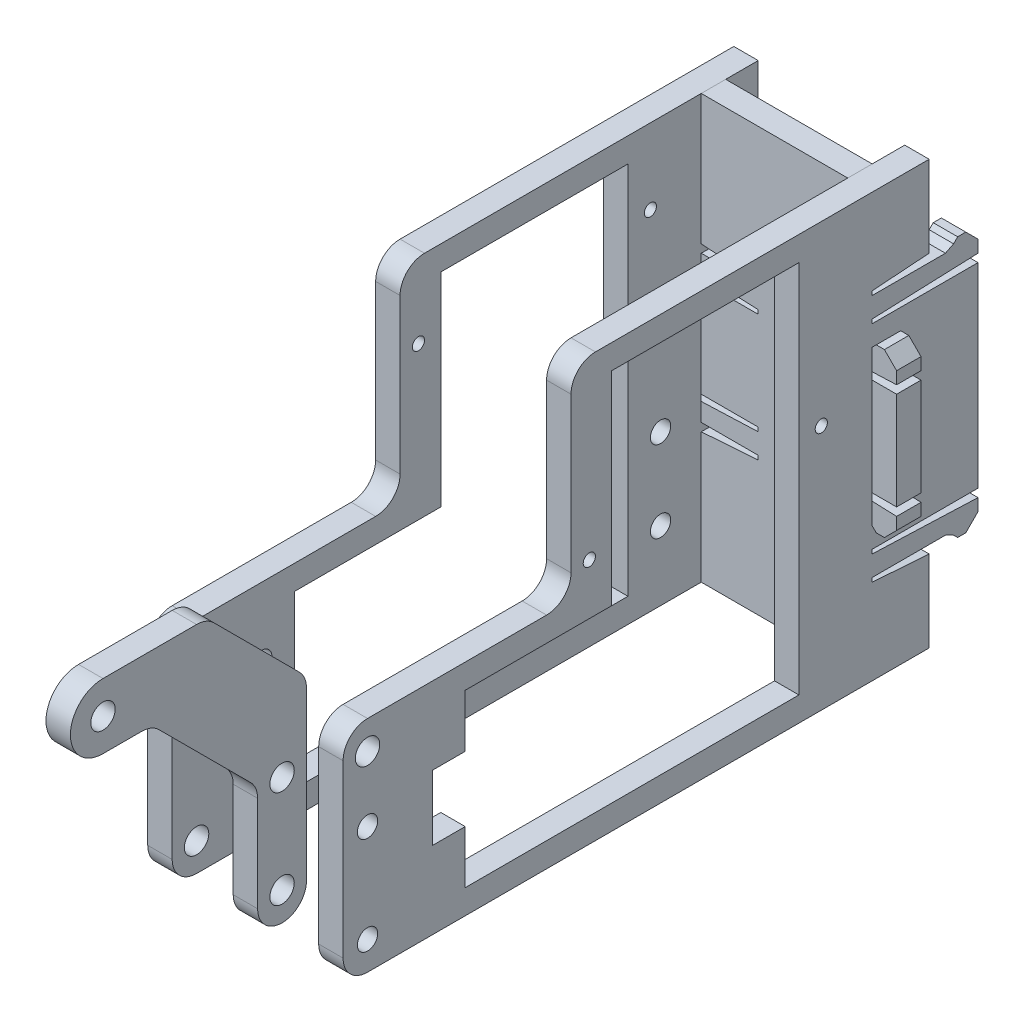
SolidWorks part; units mm, degrees
material "Lasercut ABS"
ref_plane "Front Plane" through (0, 0, 0) normal (0, 0, 1) x (1, 0, 0)
ref_plane "Top Plane" through (0, 0, 0) normal (0, 1, 0) x (1, 0, 0)
ref_plane "Right Plane" through (0, 0, 0) normal (1, 0, 0) x (0, 0, -1)
ref_plane "Plane1" through (9, 0, 0) normal (1, 0, 0) x (0, 0, -1)
ref_plane "Plane2" through (-9, 0, 0) normal (1, 0, 0) x (0, 0, -1)
sketch "Sketch1" plane through (9, 0, 0) normal (1, 0, 0) x (0, 0, -1)
  line L0 (6, 38) -> (6, 14)
  line L1 (0, 10) -> (0, 0)
  line L2 (0, 0) -> (-72, 0)
  line L3 (0, 42) -> (0, 52)
  line L4 (0, 52) -> (-44, 52)
  line L5 (-57, 17.5) -> (-57, 24)
  line L6 (-7, 35) -> (-4, 35)
  line L7 (-7, 35) -> (-7, 17)
  line L8 (-7, 17) -> (-4, 17)
  line L9 (-4, 35) -> (-4, 17)
  line L10 (-57, 3) -> (-16, 3)
  line L11 (-57, 3) -> (-57, 9.5)
  line L12 (-57, 24) -> (-16, 24) construction
  line L13 (-16, 3) -> (-16, 24) construction
  line L14 (-57, 3) -> (-16, 24) construction
  line L15 (-57, 24) -> (-16, 3) construction
  line L16 (-61, 17.5) -> (-57, 17.5)
  line L17 (-61, 17.5) -> (-61, 9.5)
  line L18 (-57, 24) -> (-39, 24)
  line L19 (-39, 24) -> (-39, 49)
  line L20 (-39, 49) -> (-16, 49)
  line L21 (-16, 49) -> (-16, 3)
  line L22 (-72, 0) -> (-72, 27)
  line L23 (-72, 27) -> (-44, 27)
  line L24 (-44, 27) -> (-44, 52)
  line L25 (-27.5, 49) -> (-27.5, 30.25) construction
  line L26 (-41.75, 30.25) -> (-13.25, 30.25) construction
  line L27 (-69, 23.5) -> (-69, 3.5) construction
  line L28 (-69, 13.5) -> (-72, 13.5) construction
  line L29 (-61, 9.5) -> (-57, 9.5)
  circle A0 centre (-69, 15.5) radius 1.25
  circle A4 centre (-41.75, 30.25) radius 0.75
  circle A5 centre (-13.25, 30.25) radius 0.75
  circle A6 centre (-69, 23.5) radius 1.5
  circle A7 centre (-69, 3.5) radius 1.25
  point P12 (-36.5, 13.5)
  point P38 (-27.5, 30.25)
  line B0 (-7, 10.5) -> (0, 10)
  line B1 (-7, 11) -> (-7, 10.5)
  line B2 (2, 11) -> (-7, 11)
  line B3 (3, 10.5) -> (2, 11)
  line B4 (3.5, 10) -> (3, 10.5)
  line B5 (4.5, 10) -> (3.5, 10)
  line B6 (6, 11.5) -> (4.5, 10)
  line B7 (6, 13) -> (6, 11.5)
  line B8 (-7, 14) -> (-7, 13.5)
  line B9 (-7, 13.5) -> (6, 13)
  line B10 (6, 14) -> (-7, 14)
  line B11 (6, 38) -> (-7, 38)
  line B12 (-7, 38) -> (-7, 38.5)
  line B13 (-7, 38.5) -> (6, 39)
  line B14 (6, 39) -> (6, 40.5)
  line B15 (6, 40.5) -> (4.5, 42)
  line B16 (4.5, 42) -> (3.5, 42)
  line B17 (3.5, 42) -> (3, 41.5)
  line B18 (3, 41.5) -> (2, 41)
  line B19 (2, 41) -> (-7, 41)
  line B20 (-7, 41) -> (-7, 41.5)
  line B21 (-7, 41.5) -> (0, 42)
  dimension "D7" = 8
  dimension "D15" = 1.5
  dimension "D20" = 3
  dimension "D9" = 2.5
  dimension "D1" = 10
  dimension "D2" = 3
  dimension "D3" = 3
  dimension "D4" = 3
  dimension "D5" = 41
  dimension "D6" = 21
  dimension "D8" = 4
  dimension "D10" = 3
  dimension "D11" = 9
  dimension "D12" = 23
  dimension "D13" = 25
  dimension "D14" = 3
  dimension "D16" = 28.5
  dimension "D17" = 18.75
  dimension "D18" = 5
  dimension "D19" = 3
  dimension "D21" = 20
  dimension "D22" = 12
  dimension "D23" = 3
  dimension "D24" = 8
sketch_block_instance "Block-Snap-L-1"
sketch_block "Block-Snap-L" parameters "D1"=13, "D2"=0.5, "D3"=1, "D4"=1.5, "D5"=1.5, "D6"=0.5, "D7"=1, "D8"=7, "D9"=1, "D10"=0.5, "D11"=1, "D12"=1.5, "D13"=2.5
sketch_block_instance "Block-Snap-R-1"
sketch_block "Block-Snap-R" parameters "D1"=13, "D2"=0.5, "D3"=1, "D4"=0.5, "D5"=1, "D6"=2.5, "D7"=1.5, "D8"=1.5, "D9"=1.5, "D10"=1, "D11"=0.5, "D12"=1, "D13"=7
extrude "Boss-Extrude1" add sketch "Sketch1" along normal blind 3
sketch "Sketch2" plane through (-9, 0, 0) normal (1, 0, 0) x (0, 0, -1)
  line L0 (-4, 35) -> (-4, 17) construction
  line L1 (-7, 35) -> (-4, 35) construction
  line L2 (-7, 35) -> (-7, 17) construction
  line L3 (-7, 17) -> (-4, 17) construction
  line L4 (-16, 49) -> (-16, 3) construction
  line L5 (-39, 49) -> (-16, 49) construction
  line L6 (-39, 24) -> (-39, 49) construction
  line L7 (-16, 3) -> (-57, 24) construction
  line L9 (-57, 3) -> (-16, 3) construction
  line L10 (0, 0) -> (-72, 0) construction
  line L11 (-72, 0) -> (-72, 27) construction
  line L12 (-72, 27) -> (-44, 27) construction
  line L13 (-44, 27) -> (-44, 52) construction
  line L14 (0, 52) -> (-44, 52) construction
  line L15 (0, 42) -> (0, 52) construction
  line L16 (-7, 41.5) -> (0, 42) construction
  line L17 (-7, 41) -> (-7, 41.5) construction
  line L18 (2, 41) -> (-7, 41) construction
  line L19 (3, 41.5) -> (2, 41) construction
  line L20 (3.5, 42) -> (3, 41.5) construction
  line L21 (4.5, 42) -> (3.5, 42) construction
  line L22 (6, 40.5) -> (4.5, 42) construction
  line L23 (6, 39) -> (6, 40.5) construction
  line L24 (-7, 38.5) -> (6, 39) construction
  line L25 (-7, 38) -> (-7, 38.5) construction
  line L26 (6, 38) -> (-7, 38) construction
  line L27 (6, 38) -> (6, 14) construction
  line L28 (6, 14) -> (-7, 14) construction
  line L29 (-7, 14) -> (-7, 13.5) construction
  line L30 (-7, 13.5) -> (6, 13) construction
  line L31 (6, 13) -> (6, 11.5) construction
  line L32 (6, 11.5) -> (4.5, 10) construction
  line L33 (4.5, 10) -> (3.5, 10) construction
  line L34 (3.5, 10) -> (3, 10.5) construction
  line L35 (3, 10.5) -> (2, 11) construction
  line L36 (2, 11) -> (-7, 11) construction
  line L37 (-7, 11) -> (-7, 10.5) construction
  line L38 (-7, 10.5) -> (0, 10) construction
  line L39 (0, 10) -> (0, 0) construction
  line L40 (-4, 35) -> (-4, 17)
  line L41 (-7, 35) -> (-4, 35)
  line L42 (-7, 35) -> (-7, 17)
  line L43 (-7, 17) -> (-4, 17)
  line L44 (-16, 49) -> (-16, 3)
  line L45 (-39, 49) -> (-16, 49)
  line L46 (-39, 24) -> (-39, 49)
  line L47 (-57, 24) -> (-39, 24) construction
  line L48 (-57, 24) -> (-39, 24)
  line L49 (-57, 3) -> (-16, 3)
  line L50 (0, 0) -> (-72, 0)
  line L51 (-72, 0) -> (-72, 27)
  line L52 (-72, 27) -> (-44, 27)
  line L53 (-44, 27) -> (-44, 52)
  line L54 (0, 52) -> (-44, 52)
  line L55 (0, 42) -> (0, 52)
  line L56 (-7, 41.5) -> (0, 42)
  line L57 (-7, 41) -> (-7, 41.5)
  line L58 (2, 41) -> (-7, 41)
  line L59 (3, 41.5) -> (2, 41)
  line L60 (3.5, 42) -> (3, 41.5)
  line L61 (4.5, 42) -> (3.5, 42)
  line L62 (6, 40.5) -> (4.5, 42)
  line L63 (6, 39) -> (6, 40.5)
  line L64 (-7, 38.5) -> (6, 39)
  line L65 (-7, 38) -> (-7, 38.5)
  line L66 (6, 38) -> (-7, 38)
  line L67 (6, 38) -> (6, 14)
  line L68 (6, 14) -> (-7, 14)
  line L69 (-7, 14) -> (-7, 13.5)
  line L70 (-7, 13.5) -> (6, 13)
  line L71 (6, 13) -> (6, 11.5)
  line L72 (6, 11.5) -> (4.5, 10)
  line L73 (4.5, 10) -> (3.5, 10)
  line L74 (3.5, 10) -> (3, 10.5)
  line L75 (3, 10.5) -> (2, 11)
  line L76 (2, 11) -> (-7, 11)
  line L77 (-7, 11) -> (-7, 10.5)
  line L78 (-7, 10.5) -> (0, 10)
  line L79 (0, 10) -> (0, 0)
  line L80 (-13.25, 42.75) -> (-41.75, 42.75) construction
  line L81 (-41.75, 42.75) -> (-41.75, 30.25) construction
  line L82 (-13.25, 42.75) -> (-13.25, 30.25) construction
  line L83 (-57, 24) -> (-57, 3)
  line L84 (-39, 24) -> (-16, 24) construction
  line L85 (-12, 8.5) -> (-61, 8.5) construction
  line L86 (-12, 8.5) -> (-12, 18.5) construction
  line L87 (-12, 18.5) -> (-61, 18.5) construction
  line L88 (-61, 8.5) -> (-61, 18.5) construction
  line L89 (-12, 8.5) -> (-61, 18.5) construction
  line L90 (-12, 18.5) -> (-61, 8.5) construction
  line L91 (-16, 24) -> (-57, 3) construction
  circle A0 centre (-69, 23.5) radius 1.5
  circle A1 centre (-69, 3.5) radius 1.5
  circle A2 centre (-69, 23.5) radius 1.5 construction
  circle A3 centre (-69, 3.5) radius 1.25 construction
  circle A4 centre (-13.25, 42.75) radius 0.75
  circle A5 centre (-41.75, 42.75) radius 0.75
  circle A6 centre (-13.25, 30.25) radius 0.75 construction
  circle A7 centre (-41.75, 30.25) radius 0.75 construction
  circle A8 centre (-12, 18.5) radius 1.25
  circle A9 centre (-12, 8.5) radius 1.25
  circle A10 centre (-61, 18.5) radius 1.25
  circle A11 centre (-61, 8.5) radius 1.25
  circle A12 centre (-69, 15.5) radius 1.5
  circle A13 centre (-69, 15.5) radius 1.25 construction
  point P58 (-36.5, 13.5)
  dimension "D1" = 3
  dimension "D5" = 2.5
  dimension "D2" = 6.25
  dimension "D3" = 10
  dimension "D4" = 49
extrude "Boss-Extrude2" add sketch "Sketch2" against normal blind 3 separate body
ref_plane "Plane3" through (0, 0, 7) normal (0, 0, -1) x (-1, 0, 0)
sketch "Sketch3" plane through (0, 0, 7) normal (0, 0, -1) x (-1, 0, 0)
  line L0 (15, 20) -> (15, 32)
  line L1 (-15, 32) -> (-15, 20)
  line L2 (-9, 36) -> (-9, 52)
  line L3 (-9, 52) -> (9, 52)
  line L4 (9, 52) -> (9, 36)
  line L5 (9, 16) -> (9, 0)
  line L6 (9, 0) -> (-9, 0)
  line L7 (-9, 0) -> (-9, 16)
  line B0 (2, 16.5) -> (9, 16)
  line B1 (2, 17) -> (2, 16.5)
  line B2 (11, 17) -> (2, 17)
  line B3 (12, 16.5) -> (11, 17)
  line B4 (12.5, 16) -> (12, 16.5)
  line B5 (13.5, 16) -> (12.5, 16)
  line B6 (15, 17.5) -> (13.5, 16)
  line B7 (15, 19) -> (15, 17.5)
  line B8 (2, 20) -> (2, 19.5)
  line B9 (2, 19.5) -> (15, 19)
  line B10 (15, 20) -> (2, 20)
  line B11 (-2, 35.5) -> (-9, 36)
  line B12 (-2, 35) -> (-2, 35.5)
  line B13 (-11, 35) -> (-2, 35)
  line B14 (-12, 35.5) -> (-11, 35)
  line B15 (-12.5, 36) -> (-12, 35.5)
  line B16 (-13.5, 36) -> (-12.5, 36)
  line B17 (-15, 34.5) -> (-13.5, 36)
  line B18 (-15, 33) -> (-15, 34.5)
  line B19 (-2, 32) -> (-2, 32.5)
  line B20 (-2, 32.5) -> (-15, 33)
  line B21 (-15, 32) -> (-2, 32)
  line B22 (15, 32) -> (2, 32)
  line B23 (2, 32) -> (2, 32.5)
  line B24 (2, 32.5) -> (15, 33)
  line B25 (15, 33) -> (15, 34.5)
  line B26 (15, 34.5) -> (13.5, 36)
  line B27 (13.5, 36) -> (12.5, 36)
  line B28 (12.5, 36) -> (12, 35.5)
  line B29 (12, 35.5) -> (11, 35)
  line B30 (11, 35) -> (2, 35)
  line B31 (2, 35) -> (2, 35.5)
  line B32 (2, 35.5) -> (9, 36)
  line B33 (-15, 20) -> (-2, 20)
  line B34 (-2, 20) -> (-2, 19.5)
  line B35 (-2, 19.5) -> (-15, 19)
  line B36 (-15, 19) -> (-15, 17.5)
  line B37 (-15, 17.5) -> (-13.5, 16)
  line B38 (-13.5, 16) -> (-12.5, 16)
  line B39 (-12.5, 16) -> (-12, 16.5)
  line B40 (-12, 16.5) -> (-11, 17)
  line B41 (-11, 17) -> (-2, 17)
  line B42 (-2, 17) -> (-2, 16.5)
  line B43 (-2, 16.5) -> (-9, 16)
sketch_block_instance "Block-Snap-L-5"
sketch_block_instance "Block-Snap-L-6"
sketch_block_instance "Block-Snap-R-3"
sketch_block_instance "Block-Snap-R-4"
extrude "Boss-Extrude3" add sketch "Sketch3" along normal blind 3 separate body contours B42 B43 L7 L6 L5 B0 B1 B2 B3 B4 B5 B6 B7 B9 B8 B10 L0 B22 B23 B24 B25 B26 B27 B28 B29 B30 B31 B32 L4 L3 L2 B11 B12 B13 B14 B15 B16 B17 B18 B20 B19 B21 L1 B33 B34 B35 B36 B37 B38 B39 B40
sketch "Sketch4" plane through (0, 0, 0) normal (1, 0, 0) x (0, 0, -1)
  line L0 (-91, 29) -> (-85, 29)
  line L1 (-72, 16) -> (-72, 0)
  line L2 (-72, 0) -> (-66, 0)
  line L3 (-66, 0) -> (-66, 24.7426)
  line L4 (-78.2574, 37) -> (-91, 37)
  line L5 (-57, 17.5) -> (-57, 24) construction
  line L6 (-57, 24) -> (-39, 24) construction
  line L7 (-85, 29) -> (-72, 16)
  line L8 (-78.2574, 37) -> (-66, 24.7426)
  circle A0 centre (-69, 23.5) radius 1.5 construction
  circle A1 centre (-69, 3.5) radius 1.5
  circle A3 centre (-69, 3.5) radius 1.25 construction
  circle A4 centre (-91, 33) radius 1.5
  arc A5 (-91, 37) -> (-91, 29) centre (-91, 33) ccw
  circle A6 centre (-69, 15.5) radius 1.5
  circle A7 centre (-69, 15.5) radius 1.25 construction
  point P0 (-69, 23.5)
  dimension "D1" = 3
  dimension "D2" = 3
  dimension "D3" = 4
  dimension "D9" = 3
  dimension "D4" = 34
  dimension "D5" = 3
  dimension "D6" = 45
  dimension "D7" = 16
  dimension "D8" = 9
extrude "Boss-Extrude4" add sketch "Sketch4" along normal mid plane 3 separate body
fillet "Fillet1" radius 3 6 edges at (0, 0, 72) (0, 0, 66) (0, 24.7426, 66) (0, 37, 78.2574) (0, 16, 72) (0, 29, 85)
fillet "Fillet2" radius 3 4 edges at (10.5, 52, 44) (10.5, 27, 44) (10.5, 27, 72) (10.5, 0, 72)
fillet "Fillet3" radius 3 4 edges at (-10.5, 0, 72) (-10.5, 27, 72) (-10.5, 27, 44) (-10.5, 52, 44)
other "Save Bodies1"
